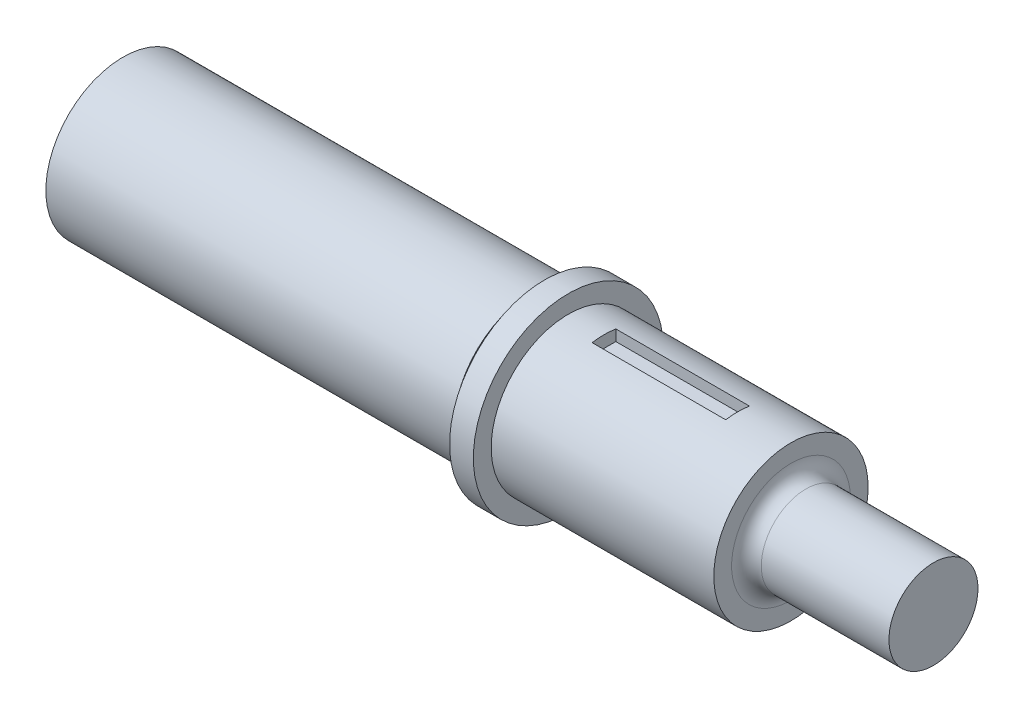
SolidWorks part; units mm, degrees
ref_plane "Front Plane" through (0, 0, 0) normal (0, 0, 1) x (1, 0, 0)
ref_plane "Top Plane" through (0, 0, 0) normal (0, 1, 0) x (1, 0, 0)
ref_plane "Right Plane" through (0, 0, 0) normal (1, 0, 0) x (0, 0, -1)
sketch "Sketch1" plane through (0, 0, 0) normal (1, 0, 0) x (0, 0, -1)
  circle A0 centre (0, 0) radius 26
extrude "Boss-Extrude1" add sketch "Sketch1" along normal blind 137.5
sketch "Sketch2" plane through (137.5, 0, 0) normal (1, 0, 0) x (0, 0, -1)
  circle A0 centre (0, 0) radius 22
extrude "Boss-Extrude2" add sketch "Sketch2" along normal blind 4.5
sketch "Sketch3" plane through (142, 0, 0) normal (1, 0, 0) x (0, 0, -1)
  circle A0 centre (0, 0) radius 32
extrude "Boss-Extrude3" add sketch "Sketch3" along normal blind 8
sketch "Sketch4" plane through (150, 0, 0) normal (1, 0, 0) x (0, 0, -1)
  circle A0 centre (0, 0) radius 26
extrude "Boss-Extrude4" add sketch "Sketch4" along normal blind 75
hole_wizard "Ø12.0 (12) Diameter Hole1" positions "3DSketch1" profile "Sketch5" hole size "Ø12.0" standard "ISO"
sketch3d "3DSketch1"
  line L0 (137.5, 0, 0) -> (0, 0, 0) construction
  point P0 (0, 0, 0)
  point P3 (0, 0, 0)
  point P6 (0, 0, 0)
  point P8 (0, 0, 0)
  point P12 (-153.5637, 12.3509, 0)
  point P14 (0, 0, 0)
  point P16 (0, 0, 0)
  point P18 (0, 0, 0)
  dimension "D1" = 0
sketch "Sketch5" plane through (0, 0, 0) normal (0, 1, 0) x (0, 0, 1)
  line L0 (0, 0) -> (0, 26.6052)
  line L1 (0, 26.6052) -> (6, 23)
  line L2 (6, 23) -> (6, 0)
  line L5 (6, 0) -> (0, 0)
  line L10 (0, 26.6052) -> (-6, 23) construction
  line L11 (0, -6.35) -> (0, 107.95) construction
  dimension "Hole Dia." = 12
  dimension "Hole Depth" = 23
  dimension "Drill Angle" = 118
sketch "Sketch6" plane through (225, 0, 0) normal (1, 0, 0) x (0, 0, -1)
  circle A0 centre (0, 0) radius 15
extrude "Boss-Extrude5" add sketch "Sketch6" along normal blind 48
cosmetic thread "Cosmetic Thread1" parameters "D1"=29, "D2"=27.797
fillet "Fillet2" radius 5 1 edges at (225, 0, -15)
sketch "Sketch7" plane through (0, 0, 0) normal (0, 1, 0) x (1, 0, 0)
  line L0 (225, 26) -> (150, 26) construction
  line L1 (162, -4) -> (207, -4)
  line L2 (162, -4) -> (162, 4)
  line L3 (162, 4) -> (207, 4)
  line L4 (207, -4) -> (207, 4)
  line L5 (150, -26) -> (225, -26) construction
  line L7 (150, -32) -> (150, 32) construction
  dimension "D1" = 30
  dimension "D2" = 30
  dimension "D4" = 12
  dimension "D3" = 45
extrude "Cut-Extrude1" cut sketch "Sketch7" against normal blind 4 from offset 26
sketch "Esquisse1" plane through (0, 0, 0) normal (-1, 0, 0) x (0, 0, 1)
  line L0 (0, -6) -> (0, -26) construction
  circle A0 centre (0, 0) radius 26 construction
  circle A4 centre (0, 0) radius 6 construction
  circle A5 centre (0, 0) radius 6 construction
  point P14 (0, -16)
  dimension "D1" = 20
  dimension "D2" = 0
hole_wizard "M8 Clearance Hole1" positions "Esquisse1" profile "Esquisse3" hole size "M8" standard "ANSI Metric"
sketch "Esquisse3" plane through (0, -16, 0) normal (0, 1, 0) x (0, 0, 1)
  line L0 (0, 0) -> (0, 15.5236)
  line L1 (0, 15.5236) -> (4.2, 13)
  line L2 (4.2, 13) -> (4.2, 0)
  line L5 (4.2, 0) -> (0, 0)
  line L10 (0, 15.5236) -> (-4.2, 13) construction
  line L11 (0, -6.35) -> (0, 107.95) construction
  dimension "Diamètre du perçage" = 8.4
  dimension "Profondeur du perçage" = 13
  dimension "Angle de pointe" = 118
sketch "Sketch8" plane through (0, 0, 0) normal (0, 0, 1) x (1, 0, 0)
  line L0 (150, 0) -> (244, 0) construction
  line L1 (150, -32) -> (150, 32) construction
  line L2 (244, 0) -> (273, 0) construction
  line L3 (273, -15) -> (273, 15) construction
  dimension "D1" = 94
  dimension "D2" = 123
sketch "Sketch9" plane through (0, 0, 0) normal (0, 0, 1) x (1, 0, 0)
  line L0 (0, 0) -> (150, 0) construction
  line L1 (0, 26) -> (0, -26) construction
  line L2 (142, 32) -> (142, -32) construction
  point P5 (142, 0)
equation "\"D2@Sketch7\"=\"D1@Sketch7\""
